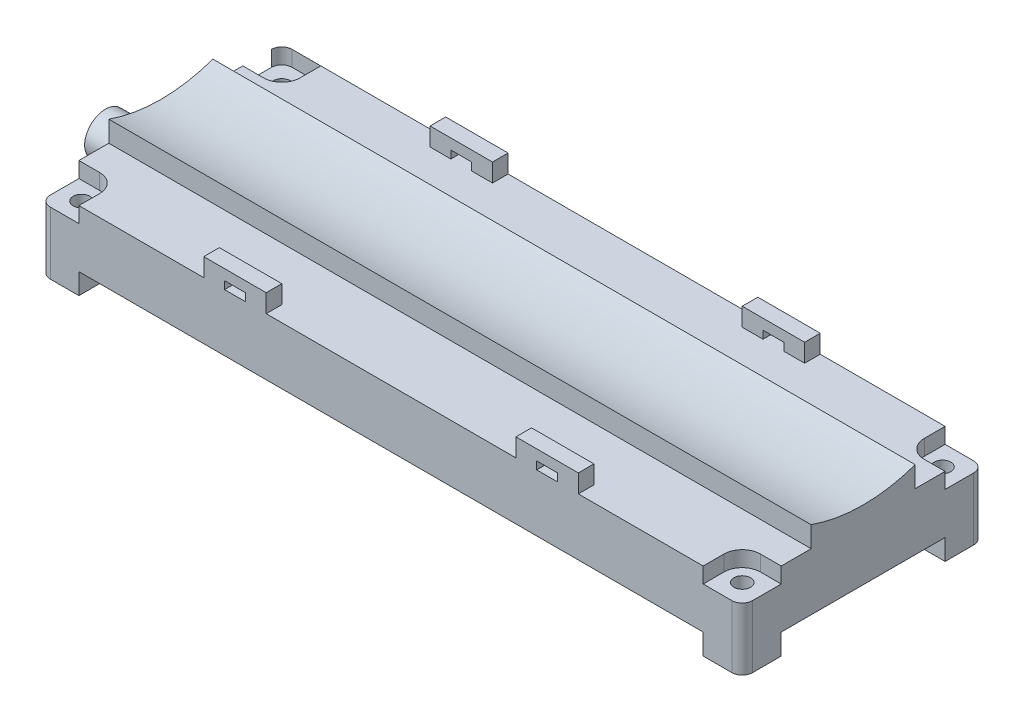
SolidWorks part; units mm, degrees
material "Nylon 6/10"
ref_plane "Front Plane" through (0, 0, 0) normal (0, 0, 1) x (1, 0, 0)
ref_plane "Top Plane" through (0, 0, 0) normal (0, 1, 0) x (1, 0, 0)
ref_plane "Right Plane" through (0, 0, 0) normal (1, 0, 0) x (0, 0, -1)
sketch "Sketch1" plane through (0, 0, 0) normal (0, 1, 0) x (1, 0, 0)
  line L0 (63.5, 19.25) -> (-63.5, 19.25) construction
  line L1 (65.5, -23.25) -> (-65.5, -23.25)
  line L2 (67.5, -21.25) -> (67.5, 21.25)
  line L3 (65.5, 23.25) -> (-65.5, 23.25)
  line L4 (-67.5, -21.25) -> (-67.5, 21.25)
  line L5 (67.5, -23.25) -> (-67.5, 23.25) construction
  line L6 (67.5, 23.25) -> (-67.5, -23.25) construction
  line L11 (-4.5, 3.75) -> (42.5, -19.25) construction
  line L12 (-4.5, -19.25) -> (42.5, 3.75) construction
  line L13 (-67.5, 0) -> (67.5, 0) construction
  line L14 (-63.5, -19.25) -> (-63.5, 19.25) construction
  line L15 (63.5, -19.25) -> (-63.5, -19.25) construction
  line L16 (63.5, -19.25) -> (63.5, 19.25) construction
  line L17 (-4.5, -19.25) -> (-4.5, 3.75) construction
  line L18 (-4.5, 3.75) -> (42.5, 3.75) construction
  line L19 (42.5, -19.25) -> (42.5, 3.75) construction
  line L20 (-4.5, -19.25) -> (42.5, -19.25) construction
  line L21 (67.5, -23.25) -> (67.5, 23.25) construction
  line L22 (67.5, -23.25) -> (-67.5, -23.25) construction
  line L23 (67.5, 23.25) -> (-67.5, 23.25) construction
  line L24 (-67.5, -23.25) -> (-67.5, 23.25) construction
  line L25 (-59.5, 0) -> (-24.5, 0) construction
  line L27 (42.5, 3.75) -> (42.5, -19.25) construction
  line L28 (-59.5, -12.4) -> (-11.5, -12.4) construction
  line L29 (34.42, -20.42) -> (57.5, -20.42) construction
  line L30 (34.42, -20.42) -> (34.42, 20.42) construction
  line L31 (34.42, 20.42) -> (57.5, 20.42) construction
  line L38 (57.5, -20.42) -> (57.5, 20.42) construction
  line L39 (34.42, -20.42) -> (57.5, 20.42) construction
  line L40 (34.42, 20.42) -> (57.5, -20.42) construction
  line L41 (-59.5, -12.4) -> (-59.5, -2.4) construction
  line L42 (-59.5, -2.4) -> (-11.5, -2.4) construction
  line L43 (-11.5, -12.4) -> (-11.5, -2.4) construction
  line L44 (-59.5, -12.4) -> (-11.5, -2.4) construction
  line L45 (-59.5, -2.4) -> (-11.5, -12.4) construction
  line L46 (-55, -17.4) -> (-16, -17.4) construction
  line L47 (-55.5, -16.9) -> (-55.5, 2.1) construction
  line L48 (-55, 2.6) -> (-16, 2.6) construction
  line L49 (-15.5, -16.9) -> (-15.5, 2.1) construction
  line L50 (-55.5, -17.4) -> (-15.5, 2.6) construction
  line L51 (-55.5, 2.6) -> (-15.5, -17.4) construction
  circle A6 centre (-63.5, 19.25) radius 2.25 construction
  circle A7 centre (-63.5, -19.25) radius 2.25 construction
  circle A8 centre (63.5, -19.25) radius 2.25 construction
  circle A9 centre (63.5, 19.25) radius 2.25 construction
  arc A16 (67.5, -21.25) -> (65.5, -23.25) centre (65.5, -21.25) cw
  arc A17 (65.5, 23.25) -> (67.5, 21.25) centre (65.5, 21.25) cw
  arc A18 (-65.5, 23.25) -> (-67.5, 21.25) centre (-65.5, 21.25) ccw
  arc A19 (-65.5, -23.25) -> (-67.5, -21.25) centre (-65.5, -21.25) cw
  arc A33 (-55.5, -16.9) -> (-55, -17.4) centre (-55, -16.9) ccw construction
  arc A34 (-16, -17.4) -> (-15.5, -16.9) centre (-16, -16.9) ccw construction
  arc A35 (-15.5, 2.1) -> (-16, 2.6) centre (-16, 2.1) ccw construction
  arc A36 (-55, 2.6) -> (-55.5, 2.1) centre (-55, 2.1) ccw construction
  circle A37 centre (-45.5, -7.4) radius 12.05 construction
  circle A38 centre (-59.5, -2.4) radius 2 construction
  circle A39 centre (-59.5, -12.4) radius 2 construction
  circle A40 centre (-11.5, -2.4) radius 2 construction
  circle A41 centre (-11.5, -12.4) radius 2 construction
  point P0 (0, 0)
  point P6 (45.96, 0)
  point P16 (-35.5, -7.4)
  point P51 (-35.5, -7.4)
  point P85 (-45.5, -7.4)
  point P92 (-45.5, 4.65)
  dimension "D6" = 4.5
  dimension "D7" = 4
  dimension "D8" = 23.08
  dimension "D9" = 40.84
  dimension "D16" = 2
  dimension "D17" = 20
  dimension "D19" = 0.5
  dimension "D20" = 10
  dimension "D22" = 4
  dimension "D23" = 4
  dimension "D26" = 47
  dimension "D11" = 10
  dimension "D21" = 24.1
  dimension "D1" = 46.5
  dimension "D2" = 135
  dimension "D4" = 48
  dimension "D5" = 35
  dimension "D10" = 10
  dimension "D12" = 8
  dimension "D14" = 25
  dimension "D18" = 40
  dimension "D13" = 23
  dimension "D27" = 2.4
  dimension "D28" = 4.65
extrude "Boss-Extrude1" add sketch "Sketch1" along normal blind 11
shell "Shell1" thickness 1 removed face at (0, 0, 0)
sketch "Sketch4" plane through (0, 10, 0) normal (0, -1, 0) x (1, 0, 0)
  line L0 (63.5, 19.25) -> (-63.5, 19.25) construction
  line L1 (65.5, -23.25) -> (60, -23.25)
  line L2 (67.5, -21.25) -> (67.5, -15.75)
  line L3 (65.5, 23.25) -> (60, 23.25)
  line L4 (-67.5, -21.25) -> (-67.5, -15.75)
  line L5 (67.5, -23.25) -> (-67.5, 23.25) construction
  line L6 (67.5, 23.25) -> (-67.5, -23.25) construction
  line L11 (-4.5, 3.75) -> (42.5, -19.25) construction
  line L12 (-4.5, -19.25) -> (42.5, 3.75) construction
  line L13 (-67.5, 0) -> (67.5, 0) construction
  line L14 (-63.5, -19.25) -> (-63.5, 19.25) construction
  line L15 (63.5, -19.25) -> (-63.5, -19.25) construction
  line L16 (63.5, -19.25) -> (63.5, 19.25) construction
  line L17 (-4.5, -19.25) -> (-4.5, 3.75) construction
  line L18 (-4.5, 3.75) -> (42.5, 3.75) construction
  line L19 (42.5, -19.25) -> (42.5, 3.75) construction
  line L20 (-4.5, -19.25) -> (42.5, -19.25) construction
  line L21 (67.5, -23.25) -> (67.5, 23.25) construction
  line L22 (67.5, -23.25) -> (-67.5, -23.25) construction
  line L23 (67.5, 23.25) -> (-67.5, 23.25) construction
  line L24 (-67.5, -23.25) -> (-67.5, 23.25) construction
  line L25 (-59.5, 0) -> (-24.5, 0) construction
  line L26 (-60, 19.25) -> (-60, 23.25)
  line L27 (42.5, 3.75) -> (42.5, -19.25) construction
  line L28 (-59.5, -12.4) -> (-11.5, -12.4) construction
  line L29 (34.42, -20.42) -> (57.5, -20.42) construction
  line L30 (34.42, -20.42) -> (34.42, 20.42) construction
  line L31 (34.42, 20.42) -> (57.5, 20.42) construction
  line L36 (-63.5, 15.75) -> (-67.5, 15.75)
  line L37 (-63.5, -15.75) -> (-67.5, -15.75)
  line L38 (57.5, -20.42) -> (57.5, 20.42) construction
  line L39 (34.42, -20.42) -> (57.5, 20.42) construction
  line L40 (34.42, 20.42) -> (57.5, -20.42) construction
  line L41 (-59.5, -12.4) -> (-59.5, -2.4) construction
  line L42 (-59.5, -2.4) -> (-11.5, -2.4) construction
  line L43 (-11.5, -12.4) -> (-11.5, -2.4) construction
  line L44 (-59.5, -12.4) -> (-11.5, -2.4) construction
  line L45 (-59.5, -2.4) -> (-11.5, -12.4) construction
  line L46 (-55, -17.4) -> (-16, -17.4) construction
  line L47 (-55.5, -16.9) -> (-55.5, 2.1) construction
  line L48 (-55, 2.6) -> (-16, 2.6) construction
  line L49 (-15.5, -16.9) -> (-15.5, 2.1) construction
  line L50 (-55.5, -17.4) -> (-15.5, 2.6) construction
  line L51 (-55.5, 2.6) -> (-15.5, -17.4) construction
  line L53 (-60, -19.25) -> (-60, -23.25)
  line L55 (-67.5, 15.75) -> (-67.5, 21.25)
  line L56 (60, 19.25) -> (60, 23.25)
  line L57 (63.5, 15.75) -> (67.5, 15.75)
  line L58 (-60, 23.25) -> (-65.5, 23.25)
  line L59 (60, -19.25) -> (60, -23.25)
  line L60 (63.5, -15.75) -> (67.5, -15.75)
  line L61 (67.5, 15.75) -> (67.5, 21.25)
  line L62 (-60, -23.25) -> (-65.5, -23.25)
  arc A6 (-63.5, 15.75) -> (-60, 19.25) centre (-63.5, 19.25) ccw
  arc A7 (-60, -19.25) -> (-63.5, -15.75) centre (-63.5, -19.25) ccw
  arc A8 (63.5, -15.75) -> (60, -19.25) centre (63.5, -19.25) ccw
  arc A9 (60, 19.25) -> (63.5, 15.75) centre (63.5, 19.25) ccw
  arc A16 (67.5, -21.25) -> (65.5, -23.25) centre (65.5, -21.25) cw
  arc A17 (65.5, 23.25) -> (67.5, 21.25) centre (65.5, 21.25) cw
  arc A18 (-65.5, 23.25) -> (-67.5, 21.25) centre (-65.5, 21.25) ccw
  arc A19 (-65.5, -23.25) -> (-67.5, -21.25) centre (-65.5, -21.25) cw
  arc A33 (-55.5, -16.9) -> (-55, -17.4) centre (-55, -16.9) ccw construction
  arc A34 (-16, -17.4) -> (-15.5, -16.9) centre (-16, -16.9) ccw construction
  arc A35 (-15.5, 2.1) -> (-16, 2.6) centre (-16, 2.1) ccw construction
  arc A36 (-55, 2.6) -> (-55.5, 2.1) centre (-55, 2.1) ccw construction
  circle A37 centre (-45.5, -7.4) radius 12.05 construction
  circle A38 centre (-59.5, -2.4) radius 2 construction
  circle A39 centre (-59.5, -12.4) radius 2 construction
  circle A40 centre (-11.5, -2.4) radius 2 construction
  circle A41 centre (-11.5, -12.4) radius 2 construction
  point P0 (0, 0)
  point P6 (45.96, 0)
  point P16 (-35.5, -7.4)
  point P51 (-35.5, -7.4)
  point P85 (-45.5, -7.4)
  point P92 (-45.5, 4.65)
  dimension "D6" = 7
  dimension "D7" = 4
  dimension "D8" = 23.08
  dimension "D9" = 40.84
  dimension "D16" = 2
  dimension "D17" = 20
  dimension "D19" = 0.5
  dimension "D20" = 10
  dimension "D22" = 4
  dimension "D23" = 4
  dimension "D26" = 47
  dimension "D11" = 10
  dimension "D21" = 24.1
  dimension "D1" = 46.5
  dimension "D2" = 135
  dimension "D4" = 48
  dimension "D5" = 35
  dimension "D10" = 10
  dimension "D12" = 8
  dimension "D14" = 25
  dimension "D18" = 40
  dimension "D13" = 23
  dimension "D27" = 2.4
  dimension "D28" = 4.65
extrude "Boss-Extrude2" add sketch "Sketch4" along normal blind 14
sketch "Sketch7" plane through (0, 10, 0) normal (0, -1, 0) x (1, 0, 0)
  line L0 (63.5, 19.25) -> (-63.5, 19.25) construction
  line L1 (65.5, -23.25) -> (60, -23.25)
  line L2 (67.5, -21.25) -> (67.5, -15.75)
  line L3 (65.5, 23.25) -> (60, 23.25)
  line L4 (-67.5, -21.25) -> (-67.5, -15.75)
  line L5 (67.5, -23.25) -> (-67.5, 23.25) construction
  line L6 (67.5, 23.25) -> (-67.5, -23.25) construction
  line L11 (-4.5, 3.75) -> (42.5, -19.25) construction
  line L12 (-4.5, -19.25) -> (42.5, 3.75) construction
  line L14 (-63.5, -19.25) -> (-63.5, 19.25) construction
  line L15 (63.5, -19.25) -> (-63.5, -19.25) construction
  line L16 (63.5, -19.25) -> (63.5, 19.25) construction
  line L17 (-4.5, -19.25) -> (-4.5, 3.75) construction
  line L18 (-4.5, 3.75) -> (42.5, 3.75) construction
  line L19 (42.5, -19.25) -> (42.5, 3.75) construction
  line L20 (-4.5, -19.25) -> (42.5, -19.25) construction
  line L21 (67.5, -23.25) -> (67.5, 23.25) construction
  line L22 (67.5, -23.25) -> (-67.5, -23.25) construction
  line L23 (67.5, 23.25) -> (-67.5, 23.25) construction
  line L24 (-67.5, -23.25) -> (-67.5, 23.25) construction
  line L25 (-59.5, 0) -> (-24.5, 0) construction
  line L27 (42.5, 3.75) -> (42.5, -19.25) construction
  line L28 (-59.5, -12.4) -> (-11.5, -12.4) construction
  line L41 (-59.5, -12.4) -> (-59.5, -2.4) construction
  line L42 (-59.5, -2.4) -> (-11.5, -2.4) construction
  line L43 (-11.5, -12.4) -> (-11.5, -2.4) construction
  line L44 (-59.5, -12.4) -> (-11.5, -2.4) construction
  line L45 (-59.5, -2.4) -> (-11.5, -12.4) construction
  line L46 (-55, -17.4) -> (-16, -17.4) construction
  line L47 (-55.5, -16.9) -> (-55.5, 2.1) construction
  line L48 (-55, 2.6) -> (-16, 2.6) construction
  line L49 (-15.5, -16.9) -> (-15.5, 2.1) construction
  line L50 (-55.5, -17.4) -> (-15.5, 2.6) construction
  line L51 (-55.5, 2.6) -> (-15.5, -17.4) construction
  line L55 (-67.5, 15.75) -> (-67.5, 21.25)
  line L58 (-60, 23.25) -> (-65.5, 23.25)
  line L61 (67.5, 15.75) -> (67.5, 21.25)
  line L62 (-60, -23.25) -> (-65.5, -23.25)
  line L67 (57, -19.25) -> (57, -19.6333)
  line L76 (63.5, 12.75) -> (70.5, 12.75) construction
  line L77 (70.5, 12.75) -> (70.5, 21.25) construction
  line L78 (65.5, 26.25) -> (57, 26.25) construction
  line L79 (57, 19.25) -> (57, 26.25) construction
  line L80 (57, -19.25) -> (57, -26.25) construction
  line L81 (65.5, -26.25) -> (57, -26.25) construction
  line L82 (70.5, -21.25) -> (70.5, -12.75) construction
  line L83 (63.5, -12.75) -> (70.5, -12.75) construction
  line L84 (-57, -19.25) -> (-57, -26.25) construction
  line L85 (-57, -26.25) -> (-65.5, -26.25) construction
  line L86 (-70.5, -21.25) -> (-70.5, -12.75) construction
  line L87 (-63.5, -12.75) -> (-70.5, -12.75) construction
  line L88 (-63.5, 12.75) -> (-70.5, 12.75) construction
  line L89 (-70.5, 12.75) -> (-70.5, 21.25) construction
  line L90 (-57, 26.25) -> (-65.5, 26.25) construction
  line L91 (-57, 19.25) -> (-57, 26.25) construction
  line L92 (63.5, 15.75) -> (67.5, 15.75) construction
  line L93 (60, 19.25) -> (60, 23.25) construction
  line L94 (57, 19.25) -> (57, 23.25)
  line L96 (57, 23.25) -> (60, 23.25)
  line L97 (63.5, 12.75) -> (67.5, 12.75)
  line L99 (67.5, 12.75) -> (67.5, 15.75)
  line L100 (63.5, -12.75) -> (67.5, -12.75)
  line L101 (57, -19.6333) -> (57, -23.25)
  line L102 (57, -23.25) -> (60, -23.25)
  line L103 (60, -19.25) -> (60, -23.25) construction
  line L104 (63.5, -15.75) -> (67.5, -15.75) construction
  line L105 (67.5, -12.75) -> (67.5, -15.75)
  line L106 (-57, -19.25) -> (-57, -23.25)
  line L107 (-57, -23.25) -> (-60, -23.25)
  line L108 (-63.5, -12.75) -> (-67.5, -12.75)
  line L109 (-67.5, -12.75) -> (-67.5, -15.75)
  line L110 (-60, -19.25) -> (-60, -23.25) construction
  line L111 (-63.5, -15.75) -> (-67.5, -15.75) construction
  line L112 (-57, 19.25) -> (-57, 23.25)
  line L113 (-57, 23.25) -> (-60, 23.25)
  line L114 (-63.5, 12.75) -> (-67.5, 12.75)
  line L115 (-67.5, 12.75) -> (-67.5, 15.75)
  line L116 (-60, 19.25) -> (-60, 23.25) construction
  line L117 (-63.5, 15.75) -> (-67.5, 15.75) construction
  arc A16 (67.5, -21.25) -> (65.5, -23.25) centre (65.5, -21.25) cw
  arc A17 (65.5, 23.25) -> (67.5, 21.25) centre (65.5, 21.25) cw
  arc A18 (-65.5, 23.25) -> (-67.5, 21.25) centre (-65.5, 21.25) ccw
  arc A19 (-65.5, -23.25) -> (-67.5, -21.25) centre (-65.5, -21.25) cw
  arc A33 (-55.5, -16.9) -> (-55, -17.4) centre (-55, -16.9) ccw construction
  arc A34 (-16, -17.4) -> (-15.5, -16.9) centre (-16, -16.9) ccw construction
  arc A35 (-15.5, 2.1) -> (-16, 2.6) centre (-16, 2.1) ccw construction
  arc A36 (-55, 2.6) -> (-55.5, 2.1) centre (-55, 2.1) ccw construction
  circle A37 centre (-45.5, -7.4) radius 12.05 construction
  circle A38 centre (-59.5, -2.4) radius 2 construction
  circle A39 centre (-59.5, -12.4) radius 2 construction
  circle A40 centre (-11.5, -2.4) radius 2 construction
  circle A41 centre (-11.5, -12.4) radius 2 construction
  arc A43 (57, 19.25) -> (63.5, 12.75) centre (63.5, 19.25) ccw
  arc A45 (63.5, -12.75) -> (57, -19.25) centre (63.5, -19.25) ccw
  arc A46 (-63.5, 12.75) -> (-57, 19.25) centre (-63.5, 19.25) ccw
  arc A49 (-57, -19.25) -> (-63.5, -12.75) centre (-63.5, -19.25) ccw
  arc A50 (65.5, 26.25) -> (70.5, 21.25) centre (65.5, 21.25) cw construction
  arc A51 (70.5, -21.25) -> (65.5, -26.25) centre (65.5, -21.25) cw construction
  arc A52 (-65.5, -26.25) -> (-70.5, -21.25) centre (-65.5, -21.25) cw construction
  arc A53 (-65.5, 26.25) -> (-70.5, 21.25) centre (-65.5, 21.25) ccw construction
  arc A54 (60, 19.25) -> (63.5, 15.75) centre (63.5, 19.25) ccw construction
  arc A55 (63.5, -15.75) -> (60, -19.25) centre (63.5, -19.25) ccw construction
  arc A56 (-60, -19.25) -> (-63.5, -15.75) centre (-63.5, -19.25) ccw construction
  arc A57 (-63.5, 15.75) -> (-60, 19.25) centre (-63.5, 19.25) ccw construction
  point P0 (0, 0)
  point P16 (-35.5, -7.4)
  point P51 (-35.5, -7.4)
  point P85 (-45.5, -7.4)
  point P92 (-45.5, 4.65)
  dimension "D7" = 4
  dimension "D16" = 2
  dimension "D17" = 20
  dimension "D19" = 0.5
  dimension "D20" = 10
  dimension "D22" = 4
  dimension "D23" = 4
  dimension "D26" = 47
  dimension "D11" = 10
  dimension "D21" = 24.1
  dimension "D1" = 46.5
  dimension "D2" = 135
  dimension "D3" = 3
  dimension "D4" = 48
  dimension "D5" = 35
  dimension "D12" = 8
  dimension "D14" = 25
  dimension "D18" = 40
  dimension "D13" = 23
extrude "Boss-Extrude3" add sketch "Sketch7" along normal blind 4
sketch "Sketch5" plane through (0, 11, 0) normal (0, 1, 0) x (1, 0, 0)
  line L1 (63.5, -19.25) -> (-63.5, -19.25) construction
  line L2 (63.5, -19.25) -> (63.5, 19.25) construction
  line L3 (63.5, 19.25) -> (-63.5, 19.25) construction
  line L4 (-63.5, -19.25) -> (-63.5, 19.25) construction
  line L5 (63.5, -19.25) -> (-63.5, 19.25) construction
  line L6 (63.5, 19.25) -> (-63.5, -19.25) construction
  circle A0 centre (-63.5, 19.25) radius 1.6
  circle A1 centre (-63.5, -19.25) radius 1.6
  circle A2 centre (63.5, 19.25) radius 1.6
  circle A3 centre (63.5, -19.25) radius 1.6
  point P0 (0, 0)
  dimension "D1" = 3.2
  dimension "D2" = 127
  dimension "D3" = 38.5
extrude "Cut-Extrude1" cut sketch "Sketch5" against normal through all both and the other way through all
sketch "Sketch12" plane through (0, 11, 0) normal (0, 1, 0) x (1, 0, 0)
  line L0 (-63.5, 15.75) -> (-67.5, 15.75)
  line L1 (-63.5, -19.25) -> (63.5, -19.25) construction
  line L2 (-63.5, -19.25) -> (-63.5, 19.25) construction
  line L3 (-63.5, 19.25) -> (63.5, 19.25) construction
  line L4 (63.5, -19.25) -> (63.5, 19.25) construction
  line L5 (-63.5, -19.25) -> (63.5, 19.25) construction
  line L6 (-63.5, 19.25) -> (63.5, -19.25) construction
  line L7 (-67.5, 15.75) -> (-67.5, 21.25)
  line L8 (-60, 19.25) -> (-60, 23.2481)
  line L9 (-60, 23.2481) -> (-65.5019, 23.2481)
  line L10 (-63.5, -15.75) -> (-67.5, -15.75)
  line L11 (-67.5, -15.75) -> (-67.5, -21.25)
  line L12 (-60, -19.25) -> (-60, -23.25)
  line L13 (-60, -23.25) -> (-65.5, -23.25)
  line L14 (60, -19.25) -> (60, -23.25)
  line L15 (60, -23.25) -> (65.5, -23.25)
  line L16 (63.5, -15.75) -> (67.5, -15.75)
  line L17 (67.5, -15.75) -> (67.5, -21.25)
  line L18 (60, 19.25) -> (60, 23.25)
  line L19 (60, 23.25) -> (65.5, 23.25)
  line L20 (63.5, 15.75) -> (67.5, 15.75)
  line L21 (67.5, 15.75) -> (67.5, 21.25)
  arc A0 (-63.5, 15.75) -> (-60, 19.25) centre (-63.5, 19.25) ccw
  arc A1 (-60, -19.25) -> (-63.5, -15.75) centre (-63.5, -19.25) ccw
  arc A2 (60, 19.25) -> (63.5, 15.75) centre (63.5, 19.25) ccw
  arc A3 (63.5, -15.75) -> (60, -19.25) centre (63.5, -19.25) ccw
  arc A4 (-67.5, 21.25) -> (-65.5019, 23.2481) centre (-65.5019, 21.25) cw
  arc A5 (-65.5, -23.25) -> (-67.5, -21.25) centre (-65.5, -21.25) cw
  arc A6 (67.5, -21.25) -> (65.5, -23.25) centre (65.5, -21.25) cw
  arc A7 (65.5, 23.25) -> (67.5, 21.25) centre (65.5, 21.25) cw
  point P0 (0, 0)
  dimension "D1" = 7
extrude "Cut-Extrude3" cut sketch "Sketch12" against normal blind 3
sketch "Sketch13" plane through (0, 10, 0) normal (0, -1, 0) x (1, 0, 0)
  circle A0 centre (-45.5, -7.4) radius 2.75
  dimension "D1" = 5.5
extrude "Boss-Extrude4" add sketch "Sketch13" along normal blind 2
sketch "Sketch14" plane through (-67.5, 0, 0) normal (-1, 0, 0) x (0, 0, 1)
  line L0 (-15.75, 11) -> (15.75, 11) construction
  line L1 (0, 0) -> (0, 11) construction
  line L2 (-15.75, 0) -> (15.75, 0) construction
  circle A1 centre (4.65, 7) radius 4
  dimension "D1" = 8
  dimension "D2" = 4
  dimension "D3" = 4.65
extrude "Boss-Extrude5" add sketch "Sketch14" along normal blind 6
sketch "Sketch15" plane through (67.5, 0, 0) normal (1, 0, 0) x (0, 0, -1)
  line L0 (-15.75, 11) -> (15.75, 11) construction
  line L1 (-10, 15) -> (10, 15) construction
  line L2 (-10, 15) -> (-10, 11)
  line L3 (-10, 11) -> (10, 11)
  line L4 (10, 15) -> (10, 11)
  line L5 (-10, 15) -> (10, 11) construction
  line L6 (-10, 11) -> (10, 15) construction
  line L7 (0, 13) -> (0, 0) construction
  line L8 (-15.75, 0) -> (15.75, 0) construction
  line L9 (0, 13) -> (0, 43.2843) construction
  arc A0 (-10, 15) -> (10, 15) centre (0, 43.2843) ccw
  point P0 (0, 13)
  point P13 (0, 43.4016)
  point P14 (0, 45.8302)
  dimension "D3" = 60
  dimension "D1" = 4
  dimension "D2" = 20
extrude "Boss-Extrude6" add sketch "Sketch15" against normal up to vertex (135 mm away) up to point (-67.5, 11, -15.75)
sketch "Sketch16" plane through (0, 0, 23.25) normal (0, 0, 1) x (1, 0, 0)
  line L0 (0, -4.584) -> (0, 31.5355) construction
  line L1 (-36, 11) -> (-32, 11)
  line L2 (-36, 11) -> (-36, 14.5)
  line L3 (-36, 14.5) -> (-24, 14.5)
  line L4 (-24, 11) -> (-24, 14.5)
  line L5 (-36, 11) -> (-24, 14.5) construction
  line L6 (-36, 14.5) -> (-24, 11) construction
  line L7 (-60, 0) -> (60, 0) construction
  line L8 (-28, 11) -> (-24, 11)
  line L9 (24, 11) -> (28, 11)
  line L10 (24, 11) -> (24, 14.5)
  line L11 (24, 14.5) -> (36, 14.5)
  line L12 (36, 11) -> (36, 14.5)
  line L13 (24, 11) -> (36, 14.5) construction
  line L14 (24, 14.5) -> (36, 11) construction
  line L20 (-32, 12.5) -> (-28, 12.5)
  line L21 (-32, 12.5) -> (-32, 11)
  line L23 (-28, 12.5) -> (-28, 11)
  line L24 (-32, 12.5) -> (-28, 11) construction
  line L25 (-32, 11) -> (-28, 12.5) construction
  line L26 (32, 11) -> (32, 12.5)
  line L27 (32, 12.5) -> (28, 12.5)
  line L28 (28, 11) -> (28, 12.5)
  line L29 (32, 11) -> (28, 12.5) construction
  line L30 (32, 12.5) -> (28, 11) construction
  line L31 (-30, 12.75) -> (-30, 11) construction
  line L32 (30, 12.75) -> (30, 11) construction
  line L33 (-60, 11) -> (60, 11) construction
  line L34 (32, 11) -> (36, 11)
  point P0 (-30, 12.75)
  point P7 (30, 12.75)
  point P14 (-30, 11.75)
  point P17 (0, 0)
  point P24 (0, 0)
  point P25 (0, 0)
  point P26 (30, 11.75)
  dimension "D1" = 30
  dimension "D2" = 30
  dimension "D3" = 12
  dimension "D4" = 12
  dimension "D5" = 3.5
  dimension "D6" = 3.5
  dimension "D7" = 1.5
  dimension "D8" = 4
extrude "Boss-Extrude7" add sketch "Sketch16" against normal blind 3
mirror "Mirror1" about plane through (0, 0, 0) normal (0, 0, 1) of "Boss-Extrude7"
